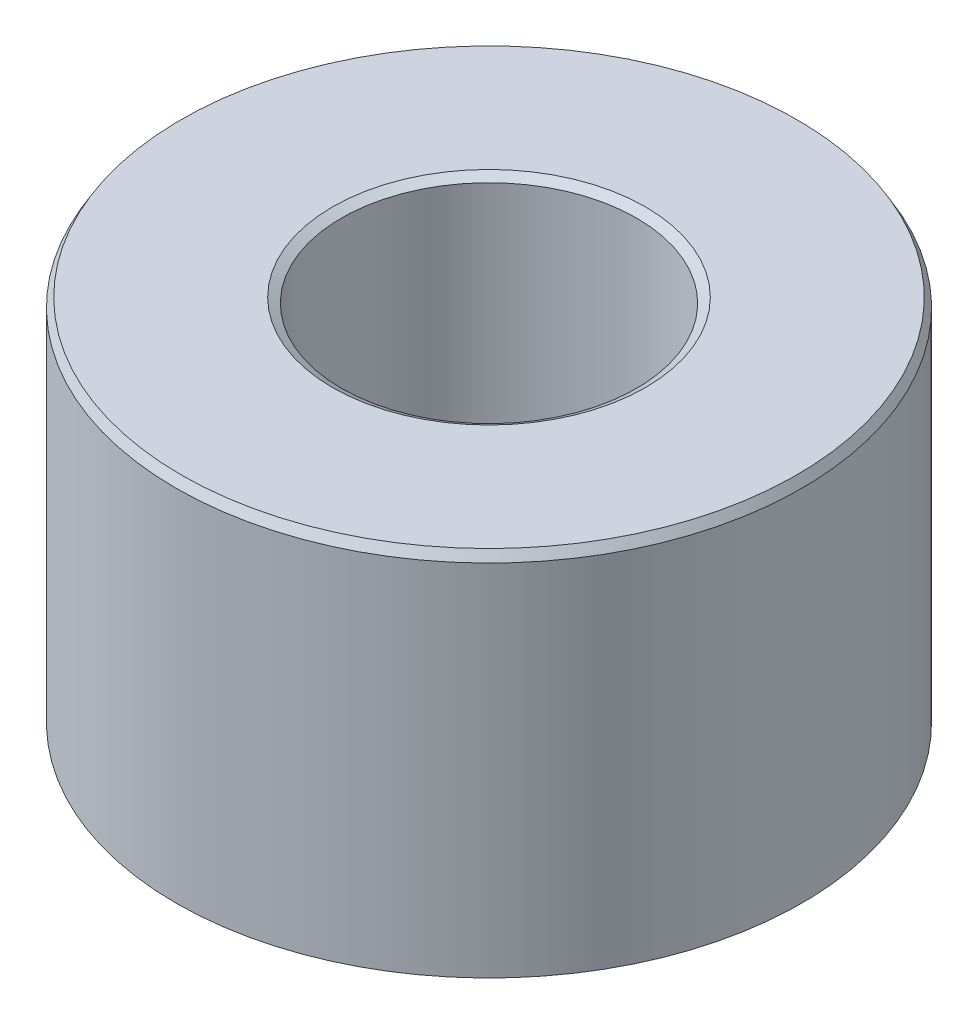
SolidWorks part; units mm, degrees
ref_plane "Front Plane" through (0, 0, 0) normal (0, 0, 1) x (1, 0, 0)
ref_plane "Top Plane" through (0, 0, 0) normal (0, 1, 0) x (1, 0, 0)
ref_plane "Right Plane" through (0, 0, 0) normal (1, 0, 0) x (0, 0, -1)
sketch "Sketch1" plane through (0, 0, 0) normal (0, 1, 0) x (1, 0, 0)
  circle A0 centre (0, 0) radius 40
  dimension "SLEEVE_OD" = 80
extrude "Boss-Extrude1" add sketch "Sketch1" along normal blind 47.7333
sketch "Sketch2" plane through (0, 0, 0) normal (0, 1, 0) x (1, 0, 0)
  circle A0 centre (0, 0) radius 18.8605
  dimension "BORE_D" = 37.7211
extrude "Cut-Extrude1" cut sketch "Sketch2" along normal through all
chamfer "Chamfer1" distance 1.1432 angle 30 4 edges at (0, 47.7333, 18.8605) (0, 0, 18.8605) (0, 0, 40) (0, 47.7333, 40) first distance on face at (0, 47.7333, 18.8605) first distance on face at (0, 0, 18.8605) first distance on face at (0, 47.7333, 40)
